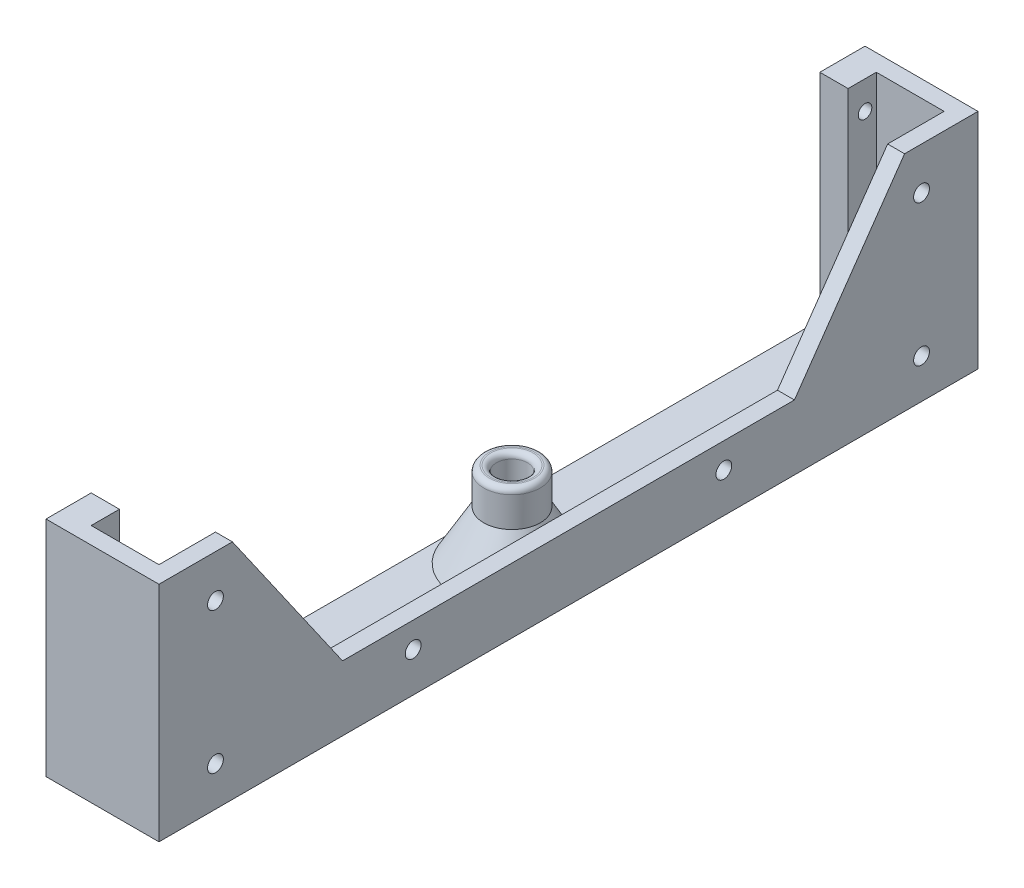
SolidWorks part; units mm, degrees
ref_plane "Спереди" through (0, 0, 0) normal (0, 0, 1) x (1, 0, 0)
ref_plane "Сверху" through (0, 0, 0) normal (0, 1, 0) x (1, 0, 0)
ref_plane "Справа" through (0, 0, 0) normal (1, 0, 0) x (0, 0, -1)
sketch "Эскиз1" plane through (0, 0, 0) normal (0, 1, 0) x (1, 0, 0)
  line L0 (0, 159.887) -> (0, 0) construction
  line L1 (0, 0) -> (281.7797, 0) construction
  line L2 (-60, -50) -> (-60, 50)
  line L3 (-20, -145) -> (20, -145)
  line L5 (-20, 145) -> (20, 145)
  line L6 (20, -145) -> (20, 145)
  line L7 (0, 145) -> (0, -145) construction
  line L8 (-435.8276, 0) -> (20, 0) construction
  line L9 (-60, 50) -> (-20, 145)
  line L10 (-60, -50) -> (-20, -145)
  point P10 (-60, 0)
  dimension "D1" = 290
  dimension "D2" = 40
  dimension "D3" = 100
  dimension "D4" = 80
extrude "Бобышка-Вытянуть1" add sketch "Эскиз1" along normal blind 4
sketch "Эскиз2" plane through (0, 0, 0) normal (0, 1, 0) x (1, 0, 0)
  line L1 (20, 145) -> (26, 145)
  line L2 (20, 145) -> (20, -145)
  line L3 (20, -145) -> (26, -145)
  line L4 (26, 145) -> (26, -145)
  dimension "D1" = 290
  dimension "D2" = 6
extrude "Бобышка-Вытянуть2" add sketch "Эскиз2" along normal blind 80
sketch "Эскиз17" plane through (0, 4, 0) normal (0, 1, 0) x (1, 0, 0)
  line L0 (-20, 145) -> (-60, 50)
  line L1 (-60, 50) -> (-60, -50)
  line L2 (-60, -50) -> (-20, -145)
  line L3 (-20, -145) -> (26, -145)
  line L4 (26, -145) -> (26, 145)
  line L5 (26, 145) -> (-20, 145)
extrude "Вытянуть-Тонкостенный1" add sketch "Эскиз17" along normal blind 96 thin thin type one direction reverse wall 6
sketch "Эскиз29" plane through (0, 100, 0) normal (0, 1, 0) x (1, 0, 0)
  line L1 (-60, 50) -> (-52, 50)
  line L2 (-60, 50) -> (-60, -50)
  line L3 (-60, -50) -> (-52, -50)
  line L4 (-52, 50) -> (-52, -50)
  dimension "D1" = 8
extrude "Бобышка-Вытянуть5" add sketch "Эскиз29" against normal blind 96
sketch "Эскиз20" plane through (-52, 0, 0) normal (1, 0, 0) x (0, 0, -1)
  line L0 (8.2314, 94.3113) -> (6.3873, 87.4288)
  line L1 (6.3, 52) -> (12.1612, 57.8612)
  line L10 (0, 0) -> (0, 100) construction
  line L12 (-48.7884, 52) -> (48.7884, 52) construction
  line L15 (-3, 95) -> (3, 95)
  line L16 (-3, 95) -> (-3, 87.8748)
  line L17 (-3, 87.8748) -> (3, 87.8748)
  line L18 (3, 95) -> (3, 87.8748)
  line L19 (0, 87.8748) -> (0, 95) construction
  line L20 (-3, 91.4374) -> (3, 91.4374) construction
  line L21 (8.2314, 94.3113) -> (14.027, 92.7584)
  line L22 (14.027, 92.7584) -> (12.1829, 85.8759)
  line L23 (6.3873, 87.4288) -> (12.1829, 85.8759)
  line L24 (18.9019, 90.7391) -> (15.3393, 84.5685)
  line L25 (18.9019, 90.7391) -> (24.0981, 87.7391)
  line L26 (24.0981, 87.7391) -> (20.5355, 81.5685)
  line L27 (15.3393, 84.5685) -> (20.5355, 81.5685)
  line L28 (28.2843, 84.5269) -> (23.246, 79.4886)
  line L29 (28.2843, 84.5269) -> (32.5269, 80.2843)
  line L30 (32.5269, 80.2843) -> (27.4886, 75.246)
  line L31 (23.246, 79.4886) -> (27.4886, 75.246)
  line L32 (35.7391, 76.0981) -> (29.5685, 72.5355)
  line L33 (35.7391, 76.0981) -> (38.7391, 70.9019)
  line L34 (38.7391, 70.9019) -> (32.5685, 67.3393)
  line L35 (29.5685, 72.5355) -> (32.5685, 67.3393)
  line L36 (40.7584, 66.027) -> (33.8759, 64.1829)
  line L37 (40.7584, 66.027) -> (42.3113, 60.2314)
  line L38 (42.3113, 60.2314) -> (35.4288, 58.3873)
  line L39 (33.8759, 64.1829) -> (35.4288, 58.3873)
  line L40 (43, 55) -> (35.8748, 55)
  line L41 (43, 55) -> (43, 49)
  line L42 (43, 49) -> (35.8748, 49)
  line L43 (35.8748, 55) -> (35.8748, 49)
  line L44 (42.3113, 43.7686) -> (35.4288, 45.6127)
  line L45 (42.3113, 43.7686) -> (40.7584, 37.973)
  line L46 (40.7584, 37.973) -> (33.8759, 39.8171)
  line L47 (35.4288, 45.6127) -> (33.8759, 39.8171)
  line L48 (38.7391, 33.0981) -> (32.5685, 36.6607)
  line L49 (38.7391, 33.0981) -> (35.7391, 27.9019)
  line L50 (35.7391, 27.9019) -> (29.5685, 31.4645)
  line L51 (32.5685, 36.6607) -> (29.5685, 31.4645)
  line L52 (32.5269, 23.7157) -> (27.4886, 28.754)
  line L53 (32.5269, 23.7157) -> (28.2843, 19.4731)
  line L54 (28.2843, 19.4731) -> (23.246, 24.5114)
  line L55 (27.4886, 28.754) -> (23.246, 24.5114)
  line L56 (24.0981, 16.2609) -> (20.5355, 22.4315)
  line L57 (24.0981, 16.2609) -> (18.9019, 13.2609)
  line L58 (18.9019, 13.2609) -> (15.3393, 19.4315)
  line L59 (20.5355, 22.4315) -> (15.3393, 19.4315)
  line L60 (14.027, 11.2416) -> (12.1829, 18.1241)
  line L61 (14.027, 11.2416) -> (8.2314, 9.6887)
  line L62 (8.2314, 9.6887) -> (6.3873, 16.5712)
  line L63 (12.1829, 18.1241) -> (6.3873, 16.5712)
  line L64 (3, 9) -> (3, 16.1252)
  line L65 (3, 9) -> (-3, 9)
  line L66 (-3, 9) -> (-3, 16.1252)
  line L67 (3, 16.1252) -> (-3, 16.1252)
  line L68 (-8.2314, 9.6887) -> (-6.3873, 16.5712)
  line L69 (-8.2314, 9.6887) -> (-14.027, 11.2416)
  line L70 (-14.027, 11.2416) -> (-12.1829, 18.1241)
  line L71 (-6.3873, 16.5712) -> (-12.1829, 18.1241)
  line L72 (-18.9019, 13.2609) -> (-15.3393, 19.4315)
  line L73 (-18.9019, 13.2609) -> (-24.0981, 16.2609)
  line L74 (-24.0981, 16.2609) -> (-20.5355, 22.4315)
  line L75 (-15.3393, 19.4315) -> (-20.5355, 22.4315)
  line L76 (-28.2843, 19.4731) -> (-23.246, 24.5114)
  line L77 (-28.2843, 19.4731) -> (-32.5269, 23.7157)
  line L78 (-32.5269, 23.7157) -> (-27.4886, 28.754)
  line L79 (-23.246, 24.5114) -> (-27.4886, 28.754)
  line L80 (-35.7391, 27.9019) -> (-29.5685, 31.4645)
  line L81 (-35.7391, 27.9019) -> (-38.7391, 33.0981)
  line L82 (-38.7391, 33.0981) -> (-32.5685, 36.6607)
  line L83 (-29.5685, 31.4645) -> (-32.5685, 36.6607)
  line L84 (-40.7584, 37.973) -> (-33.8759, 39.8171)
  line L85 (-40.7584, 37.973) -> (-42.3113, 43.7686)
  line L86 (-42.3113, 43.7686) -> (-35.4288, 45.6127)
  line L87 (-33.8759, 39.8171) -> (-35.4288, 45.6127)
  line L88 (-43, 49) -> (-35.8748, 49)
  line L89 (-43, 49) -> (-43, 55)
  line L90 (-43, 55) -> (-35.8748, 55)
  line L91 (-35.8748, 49) -> (-35.8748, 55)
  line L92 (-42.3113, 60.2314) -> (-35.4288, 58.3873)
  line L93 (-42.3113, 60.2314) -> (-40.7584, 66.027)
  line L94 (-40.7584, 66.027) -> (-33.8759, 64.1829)
  line L95 (-35.4288, 58.3873) -> (-33.8759, 64.1829)
  line L96 (-38.7391, 70.9019) -> (-32.5685, 67.3393)
  line L97 (-38.7391, 70.9019) -> (-35.7391, 76.0981)
  line L98 (-35.7391, 76.0981) -> (-29.5685, 72.5355)
  line L99 (-32.5685, 67.3393) -> (-29.5685, 72.5355)
  line L100 (-32.5269, 80.2843) -> (-27.4886, 75.246)
  line L101 (-32.5269, 80.2843) -> (-28.2843, 84.5269)
  line L102 (-28.2843, 84.5269) -> (-23.246, 79.4886)
  line L103 (-27.4886, 75.246) -> (-23.246, 79.4886)
  line L104 (-24.0981, 87.7391) -> (-20.5355, 81.5685)
  line L105 (-24.0981, 87.7391) -> (-18.9019, 90.7391)
  line L106 (-18.9019, 90.7391) -> (-15.3393, 84.5685)
  line L107 (-20.5355, 81.5685) -> (-15.3393, 84.5685)
  line L108 (-14.027, 92.7584) -> (-12.1829, 85.8759)
  line L109 (-14.027, 92.7584) -> (-8.2314, 94.3113)
  line L110 (-8.2314, 94.3113) -> (-6.3873, 87.4288)
  line L111 (-12.1829, 85.8759) -> (-6.3873, 87.4288)
  line L112 (6.276, 68.8704) -> (9.9019, 75.1506)
  line L113 (-3, 69.7482) -> (3, 69.7482)
  line L114 (-3, 69.7482) -> (-3, 77)
  line L115 (-3, 77) -> (3, 77)
  line L116 (3, 69.7482) -> (3, 77)
  line L117 (0, 77) -> (0, 69.7482) construction
  line L118 (-3, 73.3741) -> (3, 73.3741) construction
  line L119 (6.276, 68.8704) -> (11.4722, 65.8704)
  line L120 (11.4722, 65.8704) -> (15.0981, 72.1506)
  line L121 (9.9019, 75.1506) -> (15.0981, 72.1506)
  line L122 (13.8704, 63.4722) -> (20.1506, 67.0981)
  line L123 (13.8704, 63.4722) -> (16.8704, 58.276)
  line L124 (16.8704, 58.276) -> (23.1506, 61.9019)
  line L125 (20.1506, 67.0981) -> (23.1506, 61.9019)
  line L126 (17.7482, 55) -> (25, 55)
  line L127 (17.7482, 55) -> (17.7482, 49)
  line L128 (17.7482, 49) -> (25, 49)
  line L129 (25, 55) -> (25, 49)
  line L130 (16.8704, 45.724) -> (23.1506, 42.0981)
  line L131 (16.8704, 45.724) -> (13.8704, 40.5278)
  line L132 (13.8704, 40.5278) -> (20.1506, 36.9019)
  line L133 (23.1506, 42.0981) -> (20.1506, 36.9019)
  line L134 (11.4722, 38.1296) -> (15.0981, 31.8494)
  line L135 (11.4722, 38.1296) -> (6.276, 35.1296)
  line L136 (6.276, 35.1296) -> (9.9019, 28.8494)
  line L137 (15.0981, 31.8494) -> (9.9019, 28.8494)
  line L138 (3, 34.2518) -> (3, 27)
  line L139 (3, 34.2518) -> (-3, 34.2518)
  line L140 (-3, 34.2518) -> (-3, 27)
  line L141 (3, 27) -> (-3, 27)
  line L142 (-6.276, 35.1296) -> (-9.9019, 28.8494)
  line L143 (-6.276, 35.1296) -> (-11.4722, 38.1296)
  line L144 (-11.4722, 38.1296) -> (-15.0981, 31.8494)
  line L145 (-9.9019, 28.8494) -> (-15.0981, 31.8494)
  line L146 (-13.8704, 40.5278) -> (-20.1506, 36.9019)
  line L147 (-13.8704, 40.5278) -> (-16.8704, 45.724)
  line L148 (-16.8704, 45.724) -> (-23.1506, 42.0981)
  line L149 (-20.1506, 36.9019) -> (-23.1506, 42.0981)
  line L150 (-17.7482, 49) -> (-25, 49)
  line L151 (-17.7482, 49) -> (-17.7482, 55)
  line L152 (-17.7482, 55) -> (-25, 55)
  line L153 (-25, 49) -> (-25, 55)
  line L154 (-16.8704, 58.276) -> (-23.1506, 61.9019)
  line L155 (-16.8704, 58.276) -> (-13.8704, 63.4722)
  line L156 (-13.8704, 63.4722) -> (-20.1506, 67.0981)
  line L157 (-23.1506, 61.9019) -> (-20.1506, 67.0981)
  line L158 (-11.4722, 65.8704) -> (-15.0981, 72.1506)
  line L159 (-11.4722, 65.8704) -> (-6.276, 68.8704)
  line L160 (-6.276, 68.8704) -> (-9.9019, 75.1506)
  line L161 (-15.0981, 72.1506) -> (-9.9019, 75.1506)
  line L162 (6.3, 52) -> (12.1612, 46.1388)
  line L163 (-6.3, 52) -> (-12.1612, 57.8612)
  line L164 (-6.3, 52) -> (-12.1612, 46.1388)
  circle A0 centre (0, 52) radius 36 construction
  circle A1 centre (0, 52) radius 43 construction
  circle A3 centre (0, 52) radius 25 construction
  circle A4 centre (0, 52) radius 18 construction
  circle A5 centre (0, 52) radius 13.5 construction
  arc A6 (-12.1612, 57.8612) -> (12.1612, 57.8612) centre (0, 52) cw
  arc A7 (-12.1612, 46.1388) -> (12.1612, 46.1388) centre (0, 52) ccw
  point P15 (0, 91.4374)
  point P21 (0, 73.3741)
  point P112 (0, 52)
  point P163 (0, 52)
  dimension "D1" = 72
  dimension "D2" = 86
  dimension "D3" = 50
  dimension "D5" = 36
  dimension "D7" = 27
  dimension "D4" = 6
  dimension "D6" = 6
  dimension "D8" = 6.3
  dimension "D9" = 90
extrude "Вырез-Вытянуть7" cut sketch "Эскиз20" against normal blind 2
sketch "Эскиз16" plane through (26, 0, 0) normal (1, 0, 0) x (0, 0, -1)
  line L0 (0, 111.0778) -> (0, 40) construction
  line L1 (0, 40) -> (205.7417, 40) construction
  line L2 (-145, 0) -> (145, 0) construction
  line L3 (145, 100) -> (145, 0) construction
  line L4 (-162.396, 15) -> (215.9889, 15) construction
  circle A2 centre (125, 65) radius 2.8
  circle A3 centre (-125, 65) radius 2.8
  circle A4 centre (-125, 15) radius 2.8
  circle A5 centre (125, 15) radius 2.8
  circle A6 centre (55, 15) radius 2.8
  circle A7 centre (-55, 15) radius 2.8
  dimension "D2" = 5.6
  dimension "D3" = 25
  dimension "D4" = 20
  dimension "D5" = 90
  dimension "D1" = 40
extrude "Вырез-Вытянуть6" cut sketch "Эскиз16" against normal through all both and the other way through all
sketch "Эскиз21" plane through (-52, 0, 0) normal (1, 0, 0) x (0, 0, -1)
  line L0 (48.7884, 52) -> (-48.7884, 52) construction
  line L3 (0, 100) -> (0, 0) construction
  circle A0 centre (0, 52) radius 38.5 construction
  circle A1 centre (0, 90.5) radius 2
  circle A2 centre (9.9645, 89.1881) radius 2
  circle A3 centre (19.25, 85.342) radius 2
  circle A4 centre (27.2236, 79.2236) radius 2
  circle A5 centre (33.342, 71.25) radius 2
  circle A6 centre (37.1881, 61.9645) radius 2
  circle A7 centre (38.5, 52) radius 2
  circle A8 centre (37.1881, 42.0355) radius 2
  circle A9 centre (33.342, 32.75) radius 2
  circle A10 centre (27.2236, 24.7764) radius 2
  circle A11 centre (19.25, 18.658) radius 2
  circle A12 centre (9.9645, 14.8119) radius 2
  circle A13 centre (0, 13.5) radius 2
  circle A14 centre (-9.9645, 14.8119) radius 2
  circle A15 centre (-19.25, 18.658) radius 2
  circle A16 centre (-27.2236, 24.7764) radius 2
  circle A17 centre (-33.342, 32.75) radius 2
  circle A18 centre (-37.1881, 42.0355) radius 2
  circle A19 centre (-38.5, 52) radius 2
  circle A20 centre (-37.1881, 61.9645) radius 2
  circle A21 centre (-33.342, 71.25) radius 2
  circle A22 centre (-27.2236, 79.2236) radius 2
  circle A23 centre (-19.25, 85.342) radius 2
  circle A24 centre (-9.9645, 89.1881) radius 2
  circle A25 centre (0, 52) radius 21 construction
  circle A26 centre (0, 73) radius 2
  circle A27 centre (10.5, 70.1865) radius 2
  circle A28 centre (18.1865, 62.5) radius 2
  circle A29 centre (21, 52) radius 2
  circle A30 centre (18.1865, 41.5) radius 2
  circle A31 centre (10.5, 33.8135) radius 2
  circle A32 centre (0, 31) radius 2
  circle A33 centre (-10.5, 33.8135) radius 2
  circle A34 centre (-18.1865, 41.5) radius 2
  circle A35 centre (-21, 52) radius 2
  circle A36 centre (-18.1865, 62.5) radius 2
  circle A37 centre (-10.5, 70.1865) radius 2
  circle A38 centre (0, 52) radius 8.3 construction
  circle A39 centre (0, 60.3) radius 2
  circle A40 centre (7.188, 56.15) radius 2
  circle A41 centre (7.188, 47.85) radius 2
  circle A42 centre (0, 43.7) radius 2
  circle A43 centre (-7.188, 47.85) radius 2
  circle A44 centre (-7.188, 56.15) radius 2
  circle A45 centre (0, 52) radius 2
  point P64 (0, 52)
  point P90 (0, 52)
  point P104 (0, 52)
  dimension "D1" = 77
  dimension "D2" = 4
  dimension "D3" = 42
  dimension "D4" = 4
  dimension "D5" = 16.6
  dimension "D6" = 4
extrude "Отверстия под LED" cut sketch "Эскиз21" against normal blind 10
sketch "Эскиз22" plane through (0, 100, 0) normal (0, 1, 0) x (1, 0, 0)
  line L1 (26, 145) -> (-20, 145)
  line L2 (26, 145) -> (26, -145)
  line L3 (26, -145) -> (-20, -145)
  line L4 (-20, 145) -> (-20, -145)
extrude "Вырез-Вытянуть9" cut sketch "Эскиз22" against normal blind 20
fillet "Скругление3" radius 30 2 edges at (-60, 50, 50) (-60, 50, -50)
sketch "Эскиз23" plane through (-63.3172, 0, -26.6599) normal (0.9216, 0, 0.3881) x (0.3881, 0, -0.9216)
  line L0 (111.626, 100) -> (25.3247, 100) construction
  line L1 (40.9028, 100) -> (70.9028, 100)
  line L2 (40.9028, 100) -> (40.9028, 94)
  line L3 (40.9028, 94) -> (70.9028, 94)
  line L4 (70.9028, 100) -> (70.9028, 94)
  line L6 (25.9028, 4) -> (25.9028, 100) construction
  dimension "D1" = 30
  dimension "D2" = 6
  dimension "D3" = 15
extrude "Бобышка-Вытянуть3" add sketch "Эскиз23" along normal blind 10
sketch "Эскиз24" plane through (-63.3172, 0, 26.6599) normal (0.9216, 0, -0.3881) x (-0.3881, 0, -0.9216)
  line L0 (-25.3247, 100) -> (-111.626, 100) construction
  line L1 (-40.9028, 100) -> (-70.9028, 100)
  line L2 (-40.9028, 100) -> (-40.9028, 94)
  line L3 (-40.9028, 94) -> (-70.9028, 94)
  line L4 (-70.9028, 100) -> (-70.9028, 94)
  line L6 (-25.9028, 4) -> (-25.9028, 100) construction
  dimension "D1" = 30
  dimension "D2" = 6
  dimension "D3" = 15
extrude "Бобышка-Вытянуть4" add sketch "Эскиз24" along normal blind 10
chamfer "Фаска1" distance 10 angle 45 2 edges at (-41.6238, 94, -78.1819) (-41.6238, 94, 78.1819)
sketch "Эскиз27" plane through (26, 0, 0) normal (1, 0, 0) x (0, 0, -1)
  line L0 (-80, 24) -> (80, 24)
  line L1 (80, 24) -> (119, 80)
  line L2 (-145, 80) -> (145, 80) construction
  line L3 (119, 80) -> (-119, 80)
  line L4 (0, 118.8906) -> (0, 0) construction
  line L5 (-80, 24) -> (-119, 80)
  line L6 (-145, 0) -> (145, 0) construction
  line L7 (145, 80) -> (145, 0) construction
  point P10 (0, 80)
  point P11 (0, 24)
  dimension "D1" = 160
  dimension "D2" = 24
  dimension "D3" = 26
extrude "Вырез-Вытянуть10" cut sketch "Эскиз27" against normal blind 10
chamfer "Фаска2" distance 2 angle 45 24 edges at (-60, 71.25, 31.342) (-60, 61.9645, 35.1881) (-60, 52, 36.5) (-60, 42.0355, 35.1881) (-60, 32.75, 31.342) (-60, 24.7764, 25.2236) (-60, 18.658, 17.25) (-60, 14.8119, 7.9645) (-60, 13.5, -2) (-60, 14.8119, -11.9645) (-60, 18.658, -21.25) (-60, 24.7764, -29.2236) (-60, 32.75, -35.342) (-60, 42.0355, -39.1881) (-60, 52, -40.5) (-60, 61.9645, -39.1881) (-60, 71.25, -35.342) (-60, 79.2236, -29.2236) (-60, 85.342, -21.25) (-60, 89.1881, -11.9645) (-60, 90.5, -2) (-60, 79.2236, 25.2236) (-60, 85.342, 17.25) (-60, 89.1881, 7.9645)
sketch "Эскиз30" plane through (-52, 0, 0) normal (1, 0, 0) x (0, 0, -1)
  line L1 (-40, 12) -> (40, 12) construction
  line L2 (-40, 12) -> (-40, 92) construction
  line L3 (-40, 92) -> (40, 92) construction
  line L4 (40, 12) -> (40, 92) construction
  line L5 (0, 92) -> (0, 12) construction
  line L6 (-40, 52) -> (40, 52) construction
  circle A0 centre (-40, 92) radius 1.9
  circle A1 centre (40, 92) radius 1.9
  circle A2 centre (-40, 12) radius 1.9
  circle A3 centre (40, 12) radius 1.9
  point P0 (0, 52)
  dimension "D3" = 3.8
  dimension "D1" = 80
  dimension "D2" = 80
extrude "Вырез-Вытянуть11" cut sketch "Эскиз30" against normal blind 7
sketch "Эскиз32" plane through (0, 100, 0) normal (0, 1, 0) x (1, 0, 0)
  line L0 (-38, 139.8441) -> (-38, -154.1375) construction
  line L1 (-60, 43.9418) -> (-60, -43.9418) construction
  line L2 (0, 0) -> (-175.2904, 0) construction
  circle A0 centre (-38, 77.2619) radius 1.9
  circle A1 centre (-38, -77.2619) radius 1.9
  dimension "D2" = 77.2619
  dimension "D3" = 3.8
  dimension "D1" = 22
extrude "Вырез-Вытянуть13" cut sketch "Эскиз32" against normal blind 7
chamfer "Фаска3" distance 2 angle 45 7 edges at (-60, 47.85, 5.188) (-60, 43.7, -2) (-60, 47.85, -9.188) (-60, 56.15, -9.188) (-60, 52, -2) (-60, 56.15, 5.188) (-60, 60.3, -2)
chamfer "Фаска4" distance 2 angle 45 12 edges at (-60, 52, 19) (-60, 41.5, 16.1865) (-60, 33.8135, 8.5) (-60, 31, -2) (-60, 33.8135, -12.5) (-60, 41.5, -20.1865) (-60, 52, -23) (-60, 62.5, -20.1865) (-60, 70.1865, -12.5) (-60, 73, -2) (-60, 70.1865, 8.5) (-60, 62.5, 16.1865)
chamfer "Фаска5" distance 2 angle 45 6 edges at (20, 65, -127.8) (20, 15, -127.8) (20, 15, 122.2) (20, 65, 122.2) (20, 15, -57.8) (20, 15, 52.2)
sketch "Эскиз33" plane through (0, 4, 0) normal (0, 1, 0) x (1, 0, 0)
  line L0 (26, -80) -> (26, 80) construction
  circle A0 centre (6, 0) radius 10
  dimension "D1" = 20
  dimension "D2" = 20
extrude "Бобышка-Вытянуть6" add sketch "Эскиз33" along normal blind 30
chamfer "Фаска6" distance 10 angle 60 1 edges at (6, 4, -10) first distance on face at (6, 4, -10)
sketch "Эскиз34" plane through (0, 34, 0) normal (0, 1, 0) x (1, 0, 0)
  circle A0 centre (6, 0) radius 5.5
  dimension "D1" = 11
extrude "Вырез-Вытянуть14" cut sketch "Эскиз34" against normal through all both and the other way through all
fillet "Скругление4" radius 2 2 edges at (6, 34, 10) (6, 34, 5.5)
sketch "Эскиз35" plane through (0, 100, 0) normal (0, 1, 0) x (1, 0, 0)
  line L0 (26, 119) -> (26, 145) construction
  line L1 (-88.1388, -156.1498) -> (-14, -156.1498)
  line L2 (-88.1388, -156.1498) -> (-88.1388, 156.1498)
  line L3 (-88.1388, 156.1498) -> (-14, 156.1498)
  line L4 (-14, -156.1498) -> (-14, 156.1498)
  line L5 (-51.0694, 156.1498) -> (-51.0694, -156.1498) construction
  line L6 (-88.1388, 0) -> (-14, 0) construction
  point P0 (-51.0694, 0)
  dimension "D1" = 40
extrude "Вырез-Вытянуть15" cut sketch "Эскиз35" against normal through all both and the other way through all
sketch "Эскиз36" plane through (0, 4, 0) normal (0, 1, 0) x (1, 0, 0)
  line L0 (-49.1058, 0) -> (108.738, 0) construction
  line L1 (-14, 139) -> (-4, 139)
  line L2 (-14, 139) -> (-14, 129)
  line L3 (-14, 129) -> (-4, 129)
  line L4 (-4, 139) -> (-4, 129)
  line L5 (-14, -129) -> (-4, -129)
  line L6 (-4, -139) -> (-4, -129)
  line L7 (-14, -139) -> (-4, -139)
  line L8 (-14, -139) -> (-14, -129)
  dimension "D1" = 10
  dimension "D2" = 10
extrude "Бобышка-Вытянуть7" add sketch "Эскиз36" along normal up to surface (76 mm away) up to face at (10.6667, 80, -134.3333)
sketch "Эскиз37" plane through (-14, 0, 0) normal (-1, 0, 0) x (0, 0, 1)
  line L0 (-135, 80) -> (-135, -20.4461) construction
  line L1 (-145, 80) -> (-129, 80) construction
  line L2 (145, 0) -> (-145, 0) construction
  line L3 (0, -20.4461) -> (0, 97.6741) construction
  line L5 (-145, 0) -> (-145, 80) construction
  circle A0 centre (-135, 70) radius 2.4
  circle A1 centre (-135, 10) radius 2.4
  circle A2 centre (135, 10) radius 2.4
  circle A3 centre (135, 70) radius 2.4
  dimension "D1" = 4.8
  dimension "D3" = 10
  dimension "D2" = 10
  dimension "D4" = 10
extrude "Вырез-Вытянуть16" cut sketch "Эскиз37" against normal blind 20
chamfer "Фаска7" distance 1 angle 60 5 edges at (6, 0, 145) (26, 0, 0) (6, 0, -145) (6, 0, 5.5) (-14, 0, 0) first distance on face at (6, 40, 145) first distance on face at (26, 65, 127.8) first distance on face at (6, 40, -145) first distance on face at (6, 32, 5.5) first distance on face at (-14, 70, 132.6)
